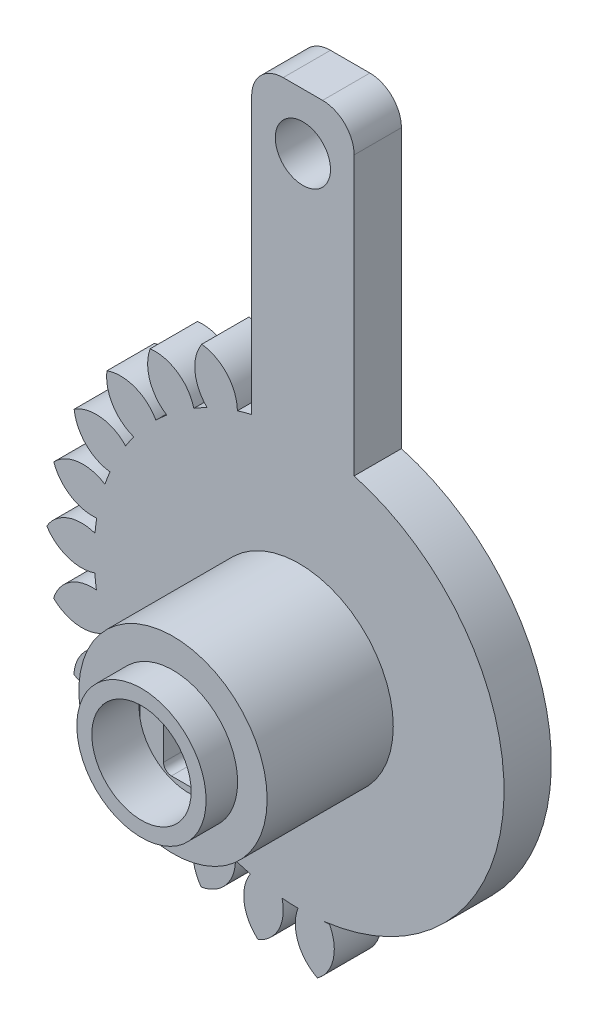
SolidWorks part; units mm, degrees
ref_plane "Front Plane" through (0, 0, 0) normal (0, 0, 1) x (1, 0, 0)
ref_plane "Top Plane" through (0, 0, 0) normal (0, 1, 0) x (1, 0, 0)
ref_plane "Right Plane" through (0, 0, 0) normal (1, 0, 0) x (0, 0, -1)
ref_plane "Plane1" through (0, 0, 5) normal (0, 0, 1) x (1, 0, 0)
ref_plane "Plane2" through (0, 0, 8) normal (0, 0, 1) x (1, 0, 0)
ref_plane "Plane3" through (0, 0, 3) normal (0, 0, 1) x (1, 0, 0)
sketch "Sketch1" plane through (0, 0, 5) normal (0, 0, 1) x (1, 0, 0)
  circle A0 centre (0, 20.9252) radius 3.9726
  circle A1 centre (0, 20.9252) radius 5
  dimension "D1" = 10
sketch "Sketch3" plane through (0, 0, 8) normal (0, 0, 1) x (1, 0, 0)
  line L0 (-3.9726, 20.9252) -> (15.3734, 20.9252) construction
  line L1 (0, 24.8978) -> (0, 8.7425) construction
  line L3 (-1.6, 23.6752) -> (1.6, 23.6752)
  line L4 (-1.6, 23.6752) -> (-1.6, 18.1752)
  line L5 (-1.6, 18.1752) -> (1.6, 18.1752)
  line L6 (1.6, 23.6752) -> (1.6, 18.1752)
  dimension "D1" = 3.2
  dimension "D2" = 5.5
  dimension "D3" = 1.6
  dimension "D4" = 2.75
extrude "Boss-Extrude1" add sketch "Sketch1" along normal blind 9 contours A0
shell "Shell1" thickness 2 removed face at (3.9726, 20.9252, 14) outward yes
extrude "Boss-Extrude2" add sketch "Sketch3" along normal blind 5 separate body
shell "Shell2" thickness 1.5 removed face at (0, 20.9252, 13) outward yes
sketch "Sketch7" plane through (0, 0, 3) normal (0, 0, -1) x (-1, 0, 0)
  line L0 (0, 14.9526) -> (0, 35.2199) construction
  line L1 (5.9726, 20.9252) -> (-26.894, 20.9252) construction
  circle A0 centre (0, 20.9252) radius 5.9726 construction
sketch "Sketch5" plane through (0, 0, 3) normal (0, 0, 1) x (1, 0, 0)
  line L1 (0, 14.9526) -> (0, 35.2199) construction
  line L2 (-5.9726, 20.9252) -> (26.894, 20.9252) construction
  circle A0 centre (0, 20.9252) radius 13
extrude "Boss-Extrude3" add sketch "Sketch5" along normal blind 3 contours A0
sketch "Sketch6" plane through (0, 0, 3) normal (0, 0, 1) x (1, 0, 0)
  line L1 (-3.01, 33.0817) -> (3.49, 33.0817)
  line L2 (-3.01, 33.0817) -> (-3.01, 53.0817)
  line L3 (-3.01, 53.0817) -> (3.49, 53.0817)
  line L4 (3.49, 33.0817) -> (3.49, 53.0817)
  dimension "D1" = 20
  dimension "D2" = 6.5
extrude "Boss-Extrude4" add sketch "Sketch6" along normal up to surface (3 mm away) up to face at (5.9726, 20.9252, 6)
sketch "Sketch8" plane through (0, 0, 3) normal (0, 0, 1) x (1, 0, 0)
  line L0 (-5.7594, 32.4645) -> (-3.9194, 33.1775)
  line L1 (0.24, 53.0817) -> (0.24, -3.388) construction
  line L2 (3.49, 53.0817) -> (-3.01, 53.0817) construction
  line L3 (13, 20.9252) -> (-7.0281, 20.9252) construction
  line L20 (-8.2588, 30.7699) -> (-6.6328, 31.8881)
  line L21 (-10.3, 28.5446) -> (-8.9758, 30.0076)
  line L22 (-11.7731, 25.9085) -> (-10.8219, 27.6375)
  line L23 (-12.5985, 23.0038) -> (-12.0717, 24.9055)
  line L24 (-12.7318, 19.987) -> (-12.6577, 21.9589)
  line L25 (-12.1657, 17.0208) -> (-12.5485, 18.9567)
  line L26 (-10.9309, 14.2651) -> (-11.7498, 16.0605)
  line L27 (-9.0939, 11.8684) -> (-10.3047, 13.4266)
  line L28 (-6.7536, 9.96) -> (-8.2911, 11.197)
  line L29 (-4.0364, 8.6427) -> (-5.8177, 9.4918)
  line L30 (-1.0886, 7.9876) -> (-3.0177, 8.403)
  line L31 (1.9309, 8.03) -> (-0.042, 7.9892)
  arc A0 (-3.9194, 33.1775) -> (-6.1748, 35.8519) centre (-6.4822, 33.3045) ccw
  arc A3 (-6.1748, 35.8519) -> (-5.7594, 32.4645) centre (-4.0035, 34.399) ccw
  arc A4 (-3.01, 33.572) -> (3.49, 33.448) centre (0, 20.9252) ccw construction
  arc A53 (-6.6328, 31.8881) -> (-9.4442, 33.9702) centre (-9.1558, 31.4205) ccw
  arc A54 (-9.4442, 33.9702) -> (-8.2588, 30.7699) centre (-6.9964, 33.0572) ccw
  arc A55 (-8.9758, 30.0076) -> (-12.1916, 31.3853) centre (-11.323, 28.9708) ccw
  arc A56 (-12.1916, 31.3853) -> (-10.3, 28.5446) centre (-9.5992, 31.0614) ccw
  arc A57 (-10.8219, 27.6375) -> (-14.2687, 28.2364) centre (-12.8667, 26.0873) ccw
  arc A58 (-14.2687, 28.2364) -> (-11.7731, 25.9085) centre (-11.6715, 28.5191) ccw
  arc A59 (-12.0717, 24.9055) -> (-15.5637, 24.6934) centre (-13.7039, 22.9256) ccw
  arc A60 (-15.5637, 24.6934) -> (-12.5985, 23.0038) centre (-13.1017, 25.5674) ccw
  arc A61 (-12.6577, 21.9589) -> (-16.0067, 20.9472) centre (-13.7893, 19.656) ccw
  arc A62 (-16.0067, 20.9472) -> (-12.7318, 19.987) centre (-13.8126, 22.3655) ccw
  arc A63 (-12.5485, 18.9567) -> (-15.5739, 17.1999) centre (-13.1185, 16.4548) ccw
  arc A64 (-15.5739, 17.1999) -> (-12.1657, 17.0208) centre (-13.766, 19.0859) ccw
  arc A65 (-11.7498, 16.0605) -> (-14.2885, 13.6534) centre (-11.7274, 13.4946) ccw
  arc A66 (-14.2885, 13.6534) -> (-10.9309, 14.2651) centre (-12.9643, 15.9055) ccw
  arc A67 (-10.3047, 13.4266) -> (-12.2199, 10.4989) centre (-9.6912, 10.9351) ccw
  arc A68 (-12.2199, 10.4989) -> (-9.0939, 11.8684) centre (-11.4507, 12.9957) ccw
  arc A69 (-8.2911, 11.197) -> (-9.4795, 7.9065) centre (-7.1197, 8.9141) ccw
  arc A70 (-9.4795, 7.9065) -> (-6.7536, 9.96) centre (-9.3069, 10.5134) ccw
  arc A71 (-5.8177, 9.4918) -> (-6.2152, 6.016) centre (-4.1513, 7.5406) ccw
  arc A72 (-6.2152, 6.016) -> (-4.0364, 8.6427) centre (-6.6484, 8.5924) ccw
  arc A73 (-3.0177, 8.403) -> (-2.6029, 4.9292) centre (-0.9462, 6.8887) ccw
  arc A74 (-2.6029, 4.9292) -> (-1.0886, 7.9876) centre (-3.6186, 7.3362) ccw
  arc A75 (-0.042, 7.9892) -> (1.1627, 4.7047) centre (2.3228, 6.9935) ccw
  arc A76 (1.1627, 4.7047) -> (1.9309, 8.03) centre (-0.3808, 6.8127) ccw
  point P26 (0.24, 20.9252)
  point P78 (0.24, 20.9252)
  point P153 (0.24, 20.9252)
  dimension "D1" = 13
extrude "Boss-Extrude5" add sketch "Sketch8" along normal up to surface (3 mm away) up to face at (3.9726, 20.9252, 6)
sketch "Sketch9" plane through (0, 0, 3) normal (0, 0, -1) x (-1, 0, 0)
  line L0 (-0.24, 53.0817) -> (-0.24, 49.0919) construction
  line L1 (-3.49, 53.0817) -> (3.01, 53.0817) construction
  circle A0 centre (-0.24, 49.5317) radius 1.75
  dimension "D1" = 3.55
extrude "Cut-Extrude1" cut sketch "Sketch9" against normal up to surface (3 mm away) up to face at (3.9726, 20.9252, 6)
fillet "Fillet1" radius 2 2 edges at (3.49, 53.0817, 4.5) (-3.01, 53.0817, 4.5)
sketch "Sketch11" plane through (0, 0, 13) normal (0, 0, 1) x (1, 0, 0)
  circle A0 centre (0, 20.9354) radius 3.15
  circle A1 centre (0, 20.9354) radius 4.1
  dimension "D1" = 6.3
  dimension "D2" = 8.2
extrude "Boss-Extrude7" add sketch "Sketch11" along normal blind 3
fillet "Fillet2" radius 0.5 4 edges at (-1.6, 18.1752, 10.5) (1.6, 18.1752, 10.5) (-1.6, 23.6752, 10.5) (1.6, 23.6752, 10.5)
